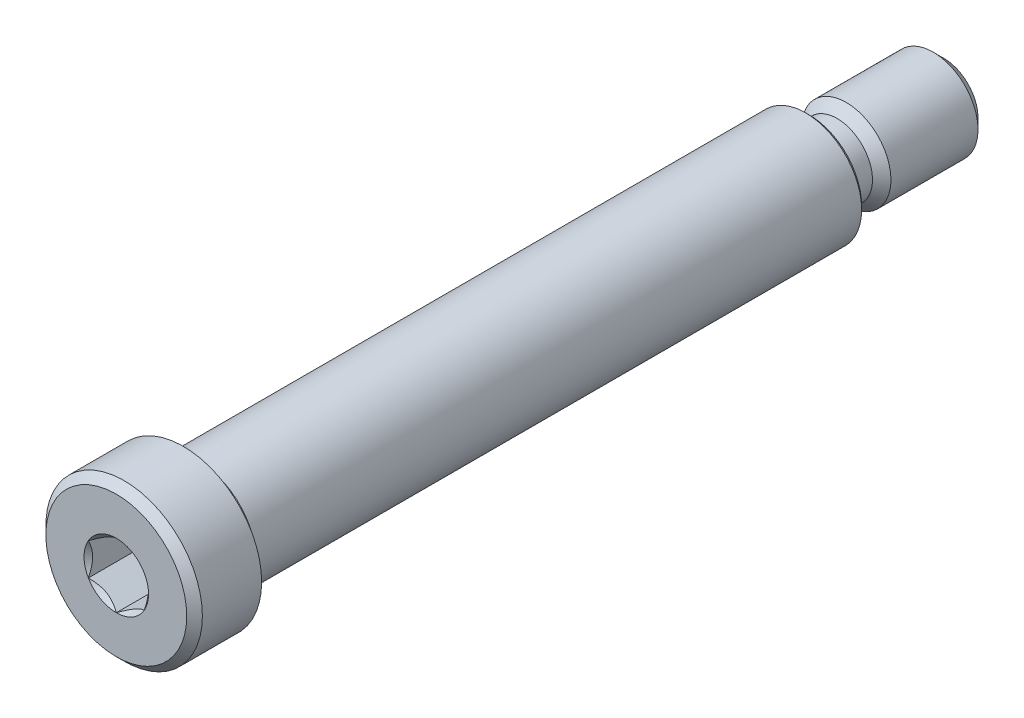
SolidWorks part; units mm, degrees
material "Cast Alloy Steel"
ref_plane "Front Plane" through (0, 0, 0) normal (0, 0, 1) x (1, 0, 0)
ref_plane "Top Plane" through (0, 0, 0) normal (0, 1, 0) x (1, 0, 0)
ref_plane "Right Plane" through (0, 0, 0) normal (1, 0, 0) x (0, 0, -1)
sketch "Sketch2" plane through (0, 0, 0) normal (1, 0, 0) x (0, 0, -1)
  line L0 (-58.7375, 0) -> (58.7375, 0) construction
  line L1 (-58.7375, 0) -> (-58.7375, 11.1125)
  line L2 (-58.7375, 11.1125) -> (-49.2125, 11.1125)
  line L3 (-49.2125, 11.1125) -> (-49.2125, 7.9375)
  line L4 (-49.2125, 7.9375) -> (39.6875, 7.9375)
  line L5 (39.6875, 6.35) -> (58.7375, 6.35)
  line L6 (58.7375, 6.35) -> (58.7375, 0)
  line L7 (58.6154, 6.5615) -> (59.5923, 4.8694) construction
  line L8 (59.5923, 4.8694) -> (60.5692, 6.5615) construction
  line L9 (60.5692, 6.5615) -> (58.6154, 6.5615) construction
  line L10 (58.7375, 6.35) -> (60.4471, 6.35) construction
  line L11 (59.5923, 6.5615) -> (59.5923, 6.35) construction
  line L12 (59.5923, 6.35) -> (59.5923, 5.0809) construction
  line L13 (59.5923, 5.0809) -> (59.5923, 4.8694) construction
  line L14 (59.4702, 5.0809) -> (59.7144, 5.0809)
  line L15 (58.6764, 6.4558) -> (60.5082, 6.4558)
  line L16 (59.7144, 5.0809) -> (60.5082, 6.4558)
  line L17 (59.4702, 5.0809) -> (58.6764, 6.4558)
  line L18 (58.7375, 0) -> (58.7375, -6.35) construction
  line L19 (39.6875, -7.9375) -> (39.6875, 0) construction
  line L20 (39.6875, 0) -> (39.6875, 7.9375) construction
  line L21 (-58.7375, 0) -> (-58.7375, -11.1125) construction
  point P11 (-46.8503, 7.9375)
  point P12 (53.8529, -6.35)
  point P22 (59.5923, 6.4558)
  point P23 (30.7975, 0)
  point P25 (-37.9603, 0)
  point P26 (-49.2125, -11.1125)
  point P29 (39.6875, -7.9375)
  dimension "Head Height" = 9.525
  dimension "Shoulder Diameter" = 15.875
  dimension "Screw Size Decimal Equivalent" = 12.7
  dimension "Thread Length" = 19.05
  dimension "Head Diameter" = 22.225
  dimension "Undercut Length" = 2.3622
  dimension "Pitch" = 1.9538
  dimension "D2" = 0.2442
  dimension "D1" = 4.8846
  dimension "Shoulder Length" = 88.9
  dimension "D4" = 8.89
  dimension "D3" = 8.89
sketch "Sketch3" plane through (0, 0, 0) normal (0, 0, 1) x (1, 0, 0)
  line L1 (0, 4.5827) -> (-3.9688, 2.2914)
  line L2 (-3.9688, 2.2914) -> (-3.9688, -2.2914)
  line L3 (-3.9688, -2.2914) -> (0, -4.5827)
  line L4 (0, -4.5827) -> (3.9688, -2.2914)
  line L5 (3.9688, -2.2914) -> (3.9688, 2.2914)
  line L6 (3.9688, 2.2914) -> (0, 4.5827)
  circle A0 centre (0, 0) radius 3.9688 construction
  dimension "Drive Size" = 7.9375
sketch "Sketch4" plane through (0, 0, 0) normal (1, 0, 0) x (0, 0, -1)
  line L0 (-49.2125, 11.1125) -> (-57.6262, 11.1125)
  line L1 (-57.6262, 11.1125) -> (-58.7375, 10.0012)
  line L2 (-49.2125, 11.1125) -> (-49.2125, 7.9375)
  line L3 (-49.2125, 7.9375) -> (-48.8156, 7.5406)
  line L4 (-48.8156, 7.5406) -> (-47.2472, 7.5406)
  line L5 (-47.2472, 7.5406) -> (-46.8503, 7.9375)
  line L6 (-49.2125, 7.9375) -> (39.6875, 7.9375) construction
  line L7 (-58.7375, 0) -> (58.7375, 0) construction
  line L8 (-46.8503, 7.9375) -> (39.1583, 7.9375)
  line L9 (39.1583, 7.9375) -> (39.6875, 7.4083)
  line L10 (39.6875, 7.4083) -> (39.6875, 0)
  line L11 (39.6875, 7.9375) -> (39.6875, 7.4083) construction
  line L12 (39.6875, 7.4083) -> (39.6875, 6.8792) construction
  line L13 (39.6875, 6.8792) -> (39.6875, 6.35) construction
  line L14 (-58.7375, 10.0012) -> (-58.7375, 0)
  line L15 (-58.7375, 11.1125) -> (-49.2125, 11.1125) construction
  line L16 (-58.7375, 0) -> (39.6875, 0)
  dimension "D1" = 45
  dimension "D2" = 15.0812
  dimension "D3" = 45
  dimension "D4" = 45
  dimension "D5" = 20.0025
revolve "Revolve1" add sketch "Sketch4" angle 360 about L16
sketch "Sketch5" plane through (0, 0, 58.7375) normal (0, 0, 1) x (1, 0, 0)
  line L0 (3.9688, 2.2914) -> (0, 4.5827) construction
  line L1 (3.9688, -2.2914) -> (3.9688, 2.2914) construction
  line L2 (0, -4.5827) -> (3.9688, -2.2914) construction
  line L3 (-3.9688, -2.2914) -> (0, -4.5827) construction
  line L4 (-3.9688, 2.2914) -> (-3.9688, -2.2914) construction
  line L5 (0, 4.5827) -> (-3.9688, 2.2914) construction
  line L6 (3.9688, 2.2914) -> (0, 4.5827)
  line L7 (3.9688, -2.2914) -> (3.9688, 2.2914)
  line L8 (0, -4.5827) -> (3.9688, -2.2914)
  line L9 (-3.9688, -2.2914) -> (0, -4.5827)
  line L10 (-3.9688, 2.2914) -> (-3.9688, -2.2914)
  line L11 (0, 4.5827) -> (-3.9688, 2.2914)
extrude "Cut-Extrude1" cut sketch "Sketch5" against normal blind 7.1437
sketch "Sketch6" plane through (0, 0, 58.7375) normal (0, 0, 1) x (1, 0, 0)
  circle A0 centre (0, 0) radius 4.5827
extrude "Cut-Extrude4" cut sketch "Sketch6" against normal blind 7.1437 draft 45
sketch "Sketch7" plane through (0, 0, 0) normal (1, 0, 0) x (0, 0, -1)
  line L0 (39.6875, 6.35) -> (57.2721, 6.35)
  line L1 (39.6875, 6.35) -> (58.7375, 6.35) construction
  line L2 (57.2721, 6.35) -> (58.7375, 4.8846)
  line L3 (58.7375, 6.35) -> (58.7375, 0) construction
  line L4 (58.7375, 4.8846) -> (58.7375, 0)
  line L5 (58.7375, 0) -> (39.6875, 0)
  line L6 (39.6875, -7.4083) -> (39.6875, 7.4083) construction
  line L7 (39.6875, 0) -> (39.6875, 6.35)
  dimension "D1" = 45
  dimension "D2" = 1.4654
revolve "Revolve2" add sketch "Sketch7" angle 360 about L5
sketch "Sketch10" plane through (0, 0, 0) normal (1, 0, 0) x (0, 0, -1)
  line L0 (40.9956, 5.0419) -> (43.5991, 5.0419)
  line L1 (43.5991, 5.0419) -> (46.4947, 7.9375)
  line L2 (46.4947, 7.9375) -> (39.6875, 7.9375)
  line L3 (39.6875, 7.9375) -> (39.6875, 6.35)
  line L4 (39.6875, -7.4083) -> (39.6875, 7.4083) construction
  line L5 (58.7375, 0) -> (39.6875, 0) construction
  line L6 (-58.7375, 0) -> (58.7375, 0) construction
  arc A0 (39.6875, 6.35) -> (40.9956, 5.0419) centre (40.9956, 6.35) ccw
  dimension "Flat OD" = 10.0838
  dimension "Flat" = 3.9116
  dimension "D3" = 45
revolve "Cut-Revolve1" cut sketch "Sketch10" angle 360 about L5
sketch "Sketch8" [suppressed] plane through (0, 0, -58.7375) normal (0, 0, -1) x (-1, 0, 0)
  circle A0 centre (0, 0) radius 6.35 construction
  circle A1 centre (0, 0) radius 6.35
curve "Helix/Spiral1" [suppressed] pitch 1.9538 height 21.0038 turns 10.75
sketch "Sketch9" [suppressed] plane through (0, 0, 0) normal (1, 0, 0) x (0, 0, -1)
  line L0 (59.4702, 5.0809) -> (59.7144, 5.0809) construction
  line L1 (59.7144, 5.0809) -> (60.5082, 6.4558) construction
  line L2 (58.6764, 6.4558) -> (60.5082, 6.4558) construction
  line L3 (59.4702, 5.0809) -> (58.6764, 6.4558) construction
  line L4 (59.4702, 5.0809) -> (59.7144, 5.0809)
  line L5 (59.7144, 5.0809) -> (60.5082, 6.4558)
  line L6 (58.6764, 6.4558) -> (60.5082, 6.4558)
  line L7 (59.4702, 5.0809) -> (58.6764, 6.4558)
ref_plane "Plane1" [suppressed] through (0, 0, -43.5991) normal (0, 0, 1) x (1, 0, 0)
split "Split1" [suppressed] bodies to split 138
sweep "Cut-Sweep1" [suppressed] cut profiles "Sketch9" path "Helix/Spiral1"
combine bodies "Combine1" [suppressed] operation type add bodies to combine 141 139
sketch "Sketch11" [suppressed] plane through (0, 0, 58.7375) normal (0, 0, 1) x (1, 0, 0)
  line L0 (-0.1604, 11.1125) -> (0.1604, 11.1125)
  line L1 (0.1604, 11.1125) -> (0, 10.8347)
  line L2 (0, 0) -> (0, 11.1125) construction
  line L3 (0, 10.8347) -> (-0.1604, 11.1125)
  line L4 (0, 0) -> (11.1125, 0) construction
  circle A0 centre (0, 0) radius 11.1125 construction
  point P6 (0, 11.1125)
  dimension "D1" = 21.6694
  dimension "D2" = 60
  dimension "D3" = 0.3208
sketch "Sketch12" [suppressed] plane through (0, 0, 0) normal (1, 0, 0) x (0, 0, -1)
  line L0 (-58.7375, 10.8347) -> (-52.2644, 10.8347)
  line L1 (-51.3159, 11.7832) -> (-51.3159, 11.1125) construction
  line L2 (-58.7375, 11.1125) -> (-49.2125, 11.1125) construction
  arc A0 (-52.2644, 10.8347) -> (-51.3159, 11.7832) centre (-52.2644, 11.7832) ccw
  point P11 (-51.5937, 11.1125)
  dimension "D1" = 2.3813
sweep "Cut-Sweep2" [suppressed] cut profiles "Sketch11" path "Sketch12"
pattern_circular "CirPattern1" [suppressed] count 76 over 360 about axis through (0, 0, 58.7375) along (0, 0, -1) of bodies 143
equation "\"D2@Sketch2\" = \"Pitch@Sketch2\" / 8"
equation "\"D1@Sketch2\"=\"Pitch@Sketch2\"*2.5"
equation "\"D2@Sketch4\"=\"Shoulder Diameter@Sketch2\"*0.95"
equation "\"D5@Sketch4\"=\"Head Diameter@Sketch2\"*0.9"
equation "\"D1@Cut-Extrude1\"=\"Head Height@Sketch2\"*0.75"
equation "\"D1@Cut-Extrude4\"=\"D1@Cut-Extrude1\""
equation "\"D2@Sketch7\"=\"pitch@sketch2\"*0.75"
equation "\"D3@Helix/Spiral1\"=\"Thread Length@Sketch2\"+\"Pitch@Sketch2\""
equation "\"D4@Helix/Spiral1\"=\"Pitch@Sketch2\""
equation "\"D1@Sketch11\"=\"Head Diameter@Sketch2\"*0.975"
equation "\"D1@Sketch12\"=\"Head Height@Sketch2\"*0.25"
equation "\"D1@CirPattern1\"=\"Head Diameter@Sketch2\" * 3.14 / \"D3@Sketch11\" * 0.35"
equation "\"D4@Sketch2\"=IF(\"Shoulder Length@Sketch2\"<1,.1,(\"Shoulder Length@Sketch2\"*.1))"
equation "\"D3@Sketch2\"=\"D4@Sketch2\""
